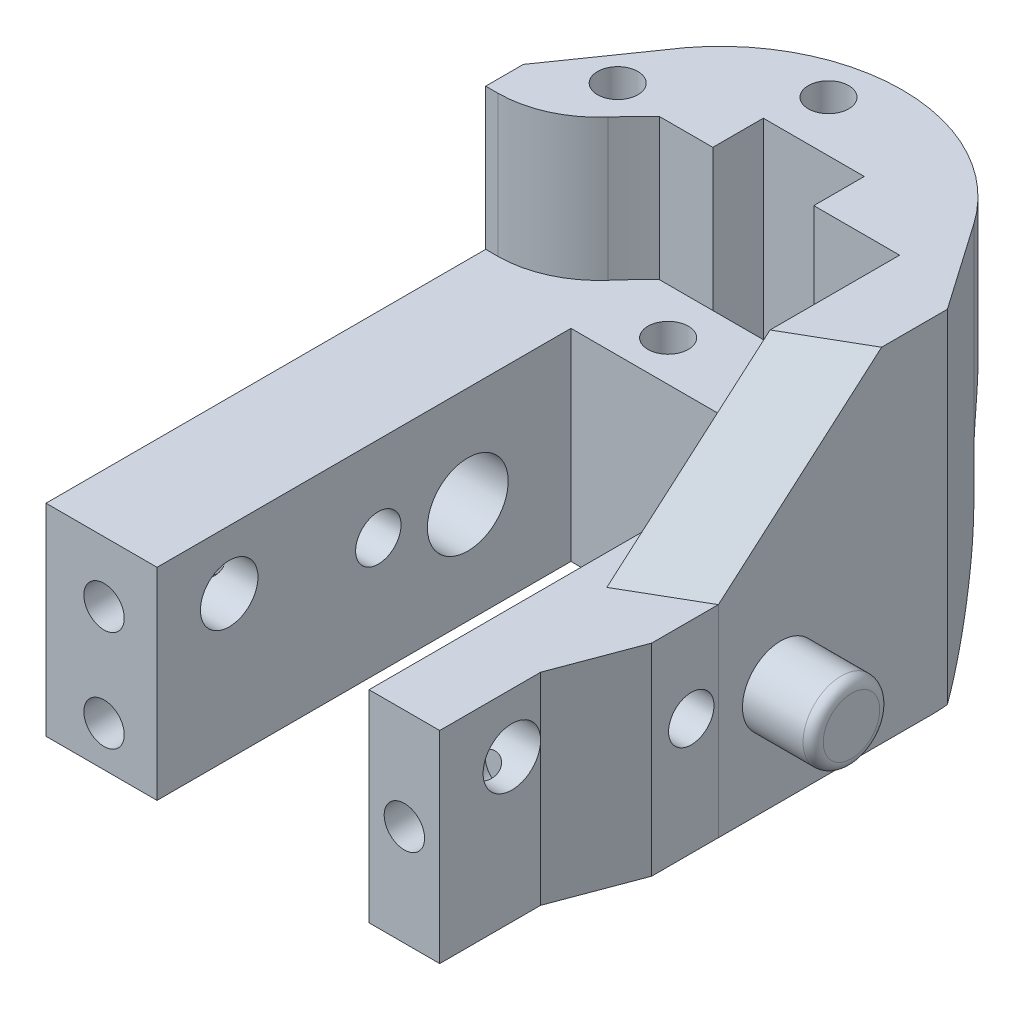
SolidWorks part; units mm, degrees
material "ABS"
ref_plane "Front Plane" through (0, 0, 0) normal (0, 0, 1) x (1, 0, 0)
ref_plane "Top Plane" through (0, 0, 0) normal (0, 1, 0) x (1, 0, 0)
ref_plane "Right Plane" through (0, 0, 0) normal (1, 0, 0) x (0, 0, -1)
sketch "Sketch1" plane through (0, 0, 0) normal (0, 1, 0) x (1, 0, 0)
  line L0 (-15.5, -37) -> (-10, -37)
  line L2 (-15.5, -37) -> (-15.5, 10)
  line L3 (-15.5, 10) -> (21, 10)
  line L4 (21, -19) -> (21, 10)
  line L5 (-10, -37) -> (-10, 4)
  line L6 (-10, 4) -> (11, 4)
  line L7 (11, 4) -> (11, -37)
  line L9 (21, -19) -> (18, -27)
  line L10 (18, -27) -> (18, -37)
  line L11 (11, -37) -> (18, -37)
  point P0 (0, 0)
  dimension "D1" = 36.5
  dimension "D2" = 7
  dimension "D3" = 21
  dimension "D4" = 10
  dimension "D5" = 21
  dimension "D6" = 41
  dimension "D7" = 47
  dimension "D8" = 8
  dimension "D9" = 5.5
  dimension "D10" = 10
extrude "Boss-Extrude1" add sketch "Sketch1" along normal blind 20
sketch "Sketch6" plane through (-15.5, 0, 0) normal (-1, 0, 0) x (0, 0, 1)
  line L1 (15, 0) -> (-10, 0)
  line L2 (15, 0) -> (15, 20)
  line L3 (15, 20) -> (-10, 20)
  line L4 (-10, 0) -> (-10, 20)
  line L5 (-10, 20) -> (-10, 0) construction
  line L7 (-10, 0) -> (37, 0) construction
  line L8 (-10, 20) -> (37, 20) construction
  dimension "D3" = 25
extrude "Boss-Extrude5" add sketch "Sketch6" along normal blind 5.5
sketch "Sketch20" plane through (0, 20, 0) normal (0, 1, 0) x (1, 0, 0)
  line L4 (-21, 6.5542) -> (14, 6.5542)
  line L11 (21.0063, -12.4007) -> (21.0063, 10.2821)
  line L12 (21.0063, 10.2821) -> (15.0032, 18.9016)
  line L13 (15.0032, 18.9016) -> (-14.9968, 18.9016)
  line L14 (-14.9968, 18.9016) -> (-21, 10.2821)
  line L15 (-21, 10) -> (-21, -15) construction
  line L16 (-21, 10.2821) -> (-21, 6.5542)
  line L18 (14, 6.5542) -> (14, -16.4458)
  line L20 (14, -16.4458) -> (21.0063, -12.4007)
  dimension "D2" = 23
  dimension "D4" = 30
  dimension "D8" = 35
  dimension "D9" = 60
  dimension "D1" = 6.0032
  dimension "D3" = 6.0032
  dimension "D5" = 8.6195
  dimension "D6" = 8.6195
  dimension "D7" = 3.7279
extrude "Boss-Extrude11" add sketch "Sketch20" along normal blind 14 and the other way up to surface (20 mm away) other way up to face at (0.5833, 0, 16.3333)
sketch "Sketch4" plane through (0, 20, 0) normal (0, 1, 0) x (1, 0, 0)
  line L2 (-10, 4) -> (11, 4) construction
  line L4 (-10, -37) -> (-10, 4) construction
  circle A6 centre (-4.375, 8) radius 2
  circle A7 centre (5.375, 8) radius 2
  dimension "D1" = 4
  dimension "D2" = 4
  dimension "D3" = 9.75
  dimension "D4" = 5.625
extrude "Cut-Extrude1" cut sketch "Sketch4" against normal blind 10
sketch "Sketch24" plane through (0, 34, 0) normal (0, 1, 0) x (1, 0, 0)
  line L0 (21.0063, 10.2821) -> (15.0032, 18.9016) construction
  line L1 (-14.9968, 18.9016) -> (-14.4209, 19.7285)
  line L2 (-21, 10.2821) -> (-21, 6.5542) construction
  line L3 (-14.9968, 18.9016) -> (-21, 10.2821) construction
  line L4 (21.0063, 10.2821) -> (15.0032, 18.9016)
  line L6 (-21, 10.2821) -> (-21, 6.5542)
  line L7 (-14.9968, 18.9016) -> (-21, 10.2821)
  line L11 (-21, 6.5542) -> (14, 6.5542) construction
  line L14 (-21, 6.5542) -> (21.0063, 6.5542)
  line L16 (21.0063, 10.2821) -> (21.0063, 6.5542)
  line L17 (21.0063, -12.4007) -> (21.0063, 10.2821) construction
  arc A3 (8.6131, 24.6437) -> (-14.4209, 19.7285) centre (-0.0555, 8.8374) ccw
  arc A4 (8.6131, 24.6437) -> (15.0032, 18.9016) centre (-0.4313, 8.152) cw
  dimension "D3" = 18.0273
  dimension "D4" = 18.8089
  dimension "D1" = 0.5759
  dimension "D2" = 1.0077
extrude "Boss-Extrude13" add sketch "Sketch24" against normal blind 12
fillet "Fillet11" radius 7.95 1 edges at (0.0032, 22, -18.9016)
sketch "Sketch22" plane through (0, 34, 0) normal (0, 1, 0) x (1, 0, 0)
  line L2 (-21, 10.2821) -> (-21, 6.5542) construction
  line L3 (-21, 6.5542) -> (14, 6.5542) construction
  circle A0 centre (-14.7203, 13.3514) radius 2
  circle A1 centre (-3.0673, 22.5813) radius 2
  dimension "D1" = 4
  dimension "D2" = 6.2797
  dimension "D3" = 6.7972
  dimension "D4" = 17.9327
  dimension "D5" = 16.0271
extrude "Cut-Extrude6" cut sketch "Sketch22" against normal blind 10
chamfer "Chamfer1" distance 14 angle 45 1 edges at (17.5032, 34, 14.4233)
sketch "Sketch26" plane through (-21, 0, 0) normal (-1, 0, 0) x (0, 0, 1)
  line L0 (15, 0) -> (37, 0)
  line L2 (37, 0) -> (37, 20)
  line L3 (37, 20) -> (15, 20)
  line L4 (15, 0) -> (15, 20) construction
  line L5 (15, 20) -> (15, 0)
extrude "Boss-Extrude14" add sketch "Sketch26" against normal up to surface (11 mm away) up to face at (-10, 10, 16.5)
sketch "Sketch25" plane through (-21, 0, 0) normal (-1, 0, 0) x (0, 0, 1)
  line L0 (11.8689, 14.9312) -> (31.15, 18.331)
  line L1 (13.2147, 7.2989) -> (32.4958, 10.6987)
  line L2 (32.4958, 10.6987) -> (31.15, 18.331) construction
  line L3 (6.2179, 10) -> (31.8229, 14.5149) construction
  line L4 (-10.2821, 0) -> (37, 0) construction
  line L5 (6.2179, 10) -> (6.2179, 38.8588) construction
  line L7 (-10.2821, 34) -> (-10.2821, 0) construction
  arc A1 (11.8689, 14.9312) -> (13.2147, 7.2989) centre (6.2179, 10) ccw
  arc A3 (31.15, 18.331) -> (32.4958, 10.6987) centre (31.8229, 14.5149) cw
  dimension "D2" = 7.75
  dimension "D1" = 7.5
  dimension "D4" = 7.75
  dimension "D3" = 26
  dimension "D5" = 80
  dimension "D7" = 10
  dimension "D6" = 16.5
  dimension "D8" = 3.875
extrude "Cut-Extrude7" cut sketch "Sketch25" against normal blind 2.5
sketch "Sketch27" plane through (-18.5, 0, 0) normal (-1, 0, 0) x (0, 0, 1)
  line L0 (6.2179, 10) -> (31.8229, 14.5149) construction
  circle A0 centre (6.2179, 10) radius 4
  circle A1 centre (15.0812, 11.5628) radius 1.15
  circle A4 centre (29.8533, 14.1676) radius 1.6
  dimension "D1" = 8
  dimension "D3" = 2.3
  dimension "D4" = 3.2
  dimension "D2" = 9
  dimension "D5" = 2
extrude "Cut-Extrude8" cut sketch "Sketch27" against normal up to next
sketch "Sketch28" plane through (-21, 0, 0) normal (-1, 0, 0) x (0, 0, 1)
  line L4 (-0.0283, 0.7779) -> (-3.1977, 15.9504)
  line L6 (13.3704, 7.7433) -> (11.8689, 14.9312) construction
  line L10 (-3.1977, 15.9504) -> (10.5064, 18.8131)
  line L11 (10.5064, 18.8131) -> (17.2487, 15.8798)
  line L13 (31.15, 18.331) -> (11.8689, 14.9312) construction
  line L14 (17.2487, 15.8798) -> (18.6801, 9.0277)
  line L16 (18.6801, 9.0277) -> (13.6759, 3.6406)
  line L17 (13.6759, 3.6406) -> (-0.0283, 0.7779)
  arc A0 (11.8689, 14.9312) -> (13.2147, 7.2989) centre (6.2179, 10) ccw construction
  circle A1 centre (6.2179, 10) radius 4 construction
  dimension "D1" = 15.5
  dimension "D2" = 7.75
  dimension "D3" = 8
  dimension "D4" = 14
  dimension "D5" = 14
  dimension "D6" = 6
  dimension "D7" = 7
extrude "Cut-Extrude9" cut sketch "Sketch28" against normal blind 2.5
sketch "Sketch31" plane through (-18.5, 0, 0) normal (-1, 0, 0) x (0, 0, 1)
  circle A0 centre (6.2179, 10) radius 4
  circle A1 centre (6.2179, 10) radius 1.65
  circle A2 centre (6.2179, 10) radius 4 construction
  dimension "D2" = 3.3
extrude "Boss-Extrude15" add sketch "Sketch31" along normal blind 1 and the other way blind 2
sketch "Sketch32" plane through (-10, 0, 0) normal (1, 0, 0) x (0, 0, -1)
  circle A0 centre (-29.8533, 14.1676) radius 2.85
  circle A3 centre (-15.0812, 11.5628) radius 2.25
  dimension "D1" = 5.7
  dimension "D2" = 4.5
extrude "Cut-Extrude12" cut sketch "Sketch32" against normal blind 7 and the other way up to next
sketch "Sketch33" plane through (21.0063, 0, 0) normal (1, 0, 0) x (0, 0, -1)
  circle A0 centre (-6.2179, 10) radius 3.8
  circle A1 centre (-6.2179, 10) radius 1.65 construction
  dimension "D1" = 7.6
extrude "Boss-Extrude17" add sketch "Sketch33" along normal blind 7
fillet "Fillet17" radius 1 1 edges at (28.0063, 10, 2.4179)
sketch "Sketch35" plane through (0, 34, 0) normal (0, 1, 0) x (1, 0, 0)
  line L0 (-21, 6.5542) -> (14, 6.5542) construction
  line L1 (-19.8, 6.5542) -> (14, 6.5542)
  line L3 (-9.8027, 12.5542) -> (14, 12.5542)
  line L4 (14, 6.5542) -> (14, 12.5542)
  line L7 (14, 6.5542) -> (14, -0.28) construction
  arc A0 (-19.8, 6.5542) -> (-12.285, 9.9568) centre (-19.8, 16.5542) ccw
  arc A1 (-12.285, 9.9568) -> (-9.8027, 12.5542) centre (19.6614, -18.0889) cw
  dimension "D3" = 42.5104
  dimension "D4" = 10
  dimension "D5" = 8.2494
  dimension "D1" = 23.8027
  dimension "D2" = 6
  dimension "D6" = 9.9972
extrude "Cut-Extrude13" cut sketch "Sketch35" against normal up to surface (14 mm away) up to face at (4.25, 20, 11.0396)
sketch "Sketch36" plane through (0, 0, 37) normal (0, 0, 1) x (1, 0, 0)
  line L0 (11, 20) -> (11, 0) construction
  line L1 (11, 20) -> (18, 20) construction
  line L2 (-21, 0) -> (-21, 20) construction
  line L6 (-21, 20) -> (-10, 20) construction
  circle A0 centre (-15.25, 14) radius 2
  circle A1 centre (14.5, 10) radius 2
  circle A2 centre (-15.25, 4) radius 2
  dimension "D3" = 4
  dimension "D1" = 5.75
  dimension "D2" = 3.5
  dimension "D4" = 10
  dimension "D5" = 6
  dimension "D6" = 5.75
  dimension "D7" = 10
extrude "Cut-Extrude14" cut sketch "Sketch36" against normal blind 10
fillet "Fillet18" radius 10 1 edges at (0.0032, 0, -18.9016)
sketch "Sketch37" plane through (21, 0, 0) normal (1, 0, 0) x (0, 0, -1)
  line L0 (-6.2179, 10) -> (6.304, 10) construction
  line L1 (4, 20) -> (4, 0) construction
  line L2 (-1.7179, 13) -> (4, 13)
  line L3 (-1.7179, 13) -> (-1.7179, 7)
  line L4 (-1.7179, 7) -> (4, 7)
  line L5 (4, 13) -> (4, 7)
  point P7 (0.043, 10)
  dimension "D1" = 6
  dimension "D2" = 3
  dimension "D4" = 4.5
extrude "Cut-Extrude16" cut sketch "Sketch37" against normal up to next
chamfer "Chamfer2" distance 7 angle 45 1 edges at (11, 10, 1.7179)
sketch "Sketch38" plane through (0, 0, 0) normal (0, -1, 0) x (1, 0, 0)
  line L0 (-10, -4) -> (11, -4) construction
  line L1 (-4.5, -4) -> (5.5, -4)
  line L2 (-4.5, -4) -> (-4.5, -24)
  line L3 (-4.5, -24) -> (5.5, -24)
  line L4 (5.5, -4) -> (5.5, -24)
  line L5 (-10, 37) -> (-10, -4) construction
  dimension "D1" = 10
  dimension "D2" = 5.5
  dimension "D3" = 20
extrude "Cut-Extrude17" cut sketch "Sketch38" against normal blind 4
sketch "Sketch39" plane through (0, 34, 0) normal (0, 1, 0) x (1, 0, 0)
  line L0 (14, 12.5542) -> (-9.8027, 12.5542) construction
  line L1 (-4.5, 12.5542) -> (5.5, 12.5542)
  line L2 (-4.5, 12.5542) -> (-4.5, 17.5542)
  line L3 (-4.5, 17.5542) -> (5.5, 17.5542)
  line L4 (5.5, 12.5542) -> (5.5, 17.5542)
  line L5 (5.5, 16.9016) -> (5.5, 4) construction
  line L6 (-4.5, 4) -> (-4.5, 16.9016) construction
  dimension "D1" = 5
extrude "Cut-Extrude19" cut sketch "Sketch39" against normal up to next
equation "\"D4@Sketch4\"=(21-\"D3@Sketch4\")/2"
equation "\"D2@Sketch37\"=\"D1@Sketch37\"/2"
equation "\"D3@Sketch20\"=\"D1@Sketch20\""
equation "\"D6@Sketch20\"=\"D5@Sketch20\""
equation "\"D5@Sketch28\"=\"D4@Sketch28\""
equation "\"D2@Sketch25\"=\"D4@Sketch25\""
equation "\"D8@Sketch25\"=\"D4@Sketch25\"/2"
